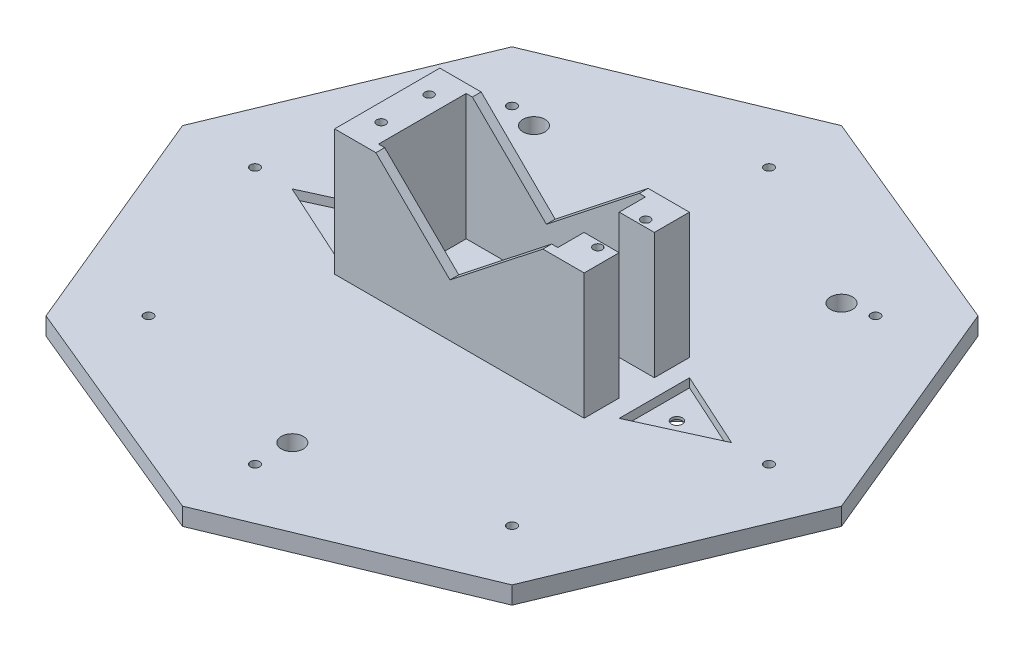
SolidWorks part; units mm, degrees
ref_plane "Ebene vorne" through (0, 0, 0) normal (0, 0, 1) x (1, 0, 0)
ref_plane "Ebene oben" through (0, 0, 0) normal (0, 1, 0) x (1, 0, 0)
ref_plane "Ebene rechts" through (0, 0, 0) normal (1, 0, 0) x (0, 0, -1)
sketch "Skizze2" plane through (0, 0, 0) normal (0, 1, 0) x (1, 0, 0)
  line L0 (-75, 0) -> (75, 0) construction
  line L1 (-55, 0) -> (55, 0) construction
  line L2 (0, -55) -> (0, 55) construction
  line L3 (-53.033, -53.033) -> (53.033, 53.033)
  line L4 (53.033, -53.033) -> (-53.033, 53.033)
  line L5 (-75, 0) -> (-53.033, 53.033)
  line L6 (-53.033, 53.033) -> (0, 75)
  line L7 (0, 75) -> (53.033, 53.033)
  line L8 (75, 0) -> (53.033, 53.033)
  line L9 (75, 0) -> (53.033, -53.033)
  line L10 (53.033, -53.033) -> (0, -75)
  line L11 (0, -75) -> (-53.033, -53.033)
  line L12 (-75, 0) -> (-53.033, -53.033)
  point P10 (0, 0)
  point P13 (0, 0)
  dimension "D1" = 150
  dimension "D2" = 75
  dimension "D3" = 150
  dimension "D4" = 150
  dimension "D5" = 45
  dimension "D6" = 45
  dimension "D7" = 75
  dimension "D8" = 75
extrude "Aufsatz-Linear austragen1" add sketch "Skizze2" along normal blind 3 and the other way blind 1 contours L7 L6 L4 L3 | L3 L0 L8 | L0 L4 L9 | L11 L10 L4 L3 | L5 L0 L4 | L0 L12 L3 region at (-42.6777, 0, -17.6777) region at (-42.6777, 0, 17.6777) region at (42.6777, 0, -17.6777) region at (0, 0, 42.6777) region at (0, 0, -42.6777) region at (42.6777, 0, 17.6777)
sketch "Skizze5" plane through (0, 0, 0) normal (0, 1, 0) x (1, 0, 0)
  line L0 (20.4, -4) -> (28.4, -4)
  line L1 (-20.4, -9.975) -> (20.4, -9.975)
  line L2 (-20.4, -9.975) -> (-20.4, 9.975)
  line L3 (-20.4, 9.975) -> (20.4, 9.975)
  line L4 (20.4, -9.975) -> (20.4, -4)
  line L5 (-20.4, -9.975) -> (20.4, 9.975) construction
  line L6 (-20.4, 9.975) -> (20.4, -9.975) construction
  line L7 (-28.4, -11.975) -> (28.4, -11.975)
  line L8 (-28.4, -11.975) -> (-28.4, 11.975)
  line L9 (-28.4, 11.975) -> (28.4, 11.975)
  line L10 (28.4, -11.975) -> (28.4, -4)
  line L11 (-28.4, -11.975) -> (28.4, 11.975) construction
  line L12 (-28.4, 11.975) -> (28.4, -11.975) construction
  line L13 (20.4, 4) -> (28.4, 4)
  line L14 (-2.2, 0) -> (2.2, 0) construction
  line L15 (20.4, 4) -> (20.4, 9.975)
  line L16 (28.4, 4) -> (28.4, 11.975)
  point P0 (0, 0)
  point P6 (0, 0)
  dimension "D1" = 40.8
  dimension "D2" = 19.95
  dimension "D3" = 2
  dimension "D4" = 8
  dimension "D5" = 4
  dimension "D6" = 4
extrude "Aufsatz-Linear austragen3" add sketch "Skizze5" along normal blind 31.65
sketch "Skizze6" plane through (0, 0, 11.975) normal (0, 0, 1) x (1, 0, 0)
  line L0 (-19, 31.65) -> (19, 31.65)
  line L1 (-28.4, 31.65) -> (28.4, 31.65) construction
  line L2 (19, 31.65) -> (-2.1527, 14.9945)
  line L3 (-2.1527, 14.9945) -> (-19, 31.65)
  line L4 (0, -2.2) -> (0, 2.2) construction
  point P5 (0, 31.65)
  dimension "D1" = 38
  dimension "D2" = 0
extrude "Schnitt-Linear austragen1" cut sketch "Skizze6" against normal blind 28.65
sketch "Skizze7" plane through (0, 3, 0) normal (0, 1, 0) x (1, 0, 0)
  line L0 (-17.9575, 0) -> (17.9575, 0) construction
  line L5 (-35, -40) -> (33.3537, 38.1186) construction
  line L6 (-33.3537, 38.1186) -> (35, -40) construction
  circle A0 centre (35, 40) radius 2.5
  circle A1 centre (-35, 40) radius 2.5
  circle A2 centre (0, -50) radius 2.5
  point P0 (0, 0)
  dimension "D3" = 5
  dimension "D4" = 5
  dimension "D5" = 5
  dimension "D6" = 50
  dimension "D1" = 80
  dimension "D2" = 70
extrude "Schnitt-Linear austragen2" cut sketch "Skizze7" against normal through all
sketch "Skizze8" plane through (0, 3, 0) normal (0, 1, 0) x (1, 0, 0)
  line L0 (-75, 0) -> (75, 0) construction
  line L7 (-32.4, 8.05) -> (-32.4, -8.05)
  line L8 (-44.1054, 2.719) -> (-32.4, -8.05) construction
  line L9 (-44.1054, -2.719) -> (-32.4, 8.05) construction
  line L12 (32.4, 8.0043) -> (32.4, -8.0043)
  line L15 (32.4, 8.0043) -> (44.0833, -2.6833) construction
  line L16 (32.4, -8.0043) -> (44.0833, 2.6833) construction
  line L17 (28.4, -11.975) -> (28.4, -4) construction
  line L18 (-28.4, 11.975) -> (-28.4, -11.975) construction
  line L19 (-50.0756, 0) -> (-32.4, -8.05)
  line L21 (-32.4, 8.05) -> (-50.0756, 0)
  line L22 (32.4, -8.0043) -> (49.9752, 0)
  line L23 (49.9752, 0) -> (32.4, 8.0043)
  line L24 (32.4, -8.0043) -> (32.4, 8.0043)
  point P2 (-41.15, 0)
  point P7 (41.15, 0)
  dimension "D1" = 4
  dimension "D2" = 4
  dimension "D3" = 16.1
extrude "Schnitt-Linear austragen6" cut sketch "Skizze8" against normal blind 2 contours L7 L21 L19 | L22 L23 L12 region at (-38.2919, 3, 0) region at (38.2584, 3, 0)
sketch "Skizze9" plane through (0, 31.65, 0) normal (0, 1, 0) x (1, 0, 0)
  circle A0 centre (-24.4, -5.375) radius 1
  circle A1 centre (-24.4, 5.525) radius 1
  circle A2 centre (24.9, 5.525) radius 1
  circle A3 centre (24.9, -5.375) radius 1
  dimension "D1" = 2
  dimension "D2" = 2
  dimension "D3" = 2
  dimension "D4" = 2
extrude "Schnitt-Linear austragen5" cut sketch "Skizze9" against normal blind 13.1
sketch "Skizze10" plane through (0, 1, 0) normal (0, 1, 0) x (1, 0, 0)
  line L1 (-0.013, 21.1078) -> (0.0217, -30.9037) construction
  line L7 (41.9977, 0.05) -> (22.7023, 0.05) construction
  line L8 (-28.4, 11.975) -> (-28.4, -11.975) construction
  line L9 (28.4, 4) -> (28.4, 11.975) construction
  circle A0 centre (-37.4878, 0) radius 1.25
  circle A1 centre (37.49, 0.05) radius 1.25
  dimension "D1" = 2.5
  dimension "D2" = 0
  dimension "D3" = 9.0878
  dimension "D4" = 9.09
extrude "Schnitt-Linear austragen7" cut sketch "Skizze10" against normal through all
sketch "Skizze11" plane through (0, -1, 0) normal (0, -1, 0) x (1, 0, 0)
  circle A0 centre (-37.4878, 0) radius 2.75
  circle A1 centre (37.49, -0.05) radius 2.75
  dimension "D1" = 5.5
  dimension "D2" = 5.5
extrude "Schnitt-Linear austragen8" cut sketch "Skizze11" against normal blind 1.4
sketch "Skizze14" plane through (0, 3, 0) normal (0, 1, 0) x (1, 0, 0)
  line L0 (0, 0) -> (-51.0988, 51.0988) construction
  line L1 (-51.0988, 51.0988) -> (0, 0) construction
  line L2 (0, 0) -> (44.6211, 44.6211) construction
  line L3 (44.6211, 44.6211) -> (0, 0) construction
  line L4 (0, 0) -> (42.9287, -42.9287) construction
  line L5 (42.9287, -42.9287) -> (0, 0) construction
  line L6 (0, 0) -> (-43.4336, -43.4336) construction
  circle A1 centre (-58.5, 0) radius 1.05
  circle A2 centre (0, 58.5) radius 1.05
  circle A3 centre (-41.3657, 41.3657) radius 1.05
  circle A4 centre (41.3657, 41.3657) radius 1.05
  circle A5 centre (58.5, 0) radius 1.05
  circle A6 centre (41.3657, -41.3657) radius 1.05
  circle A7 centre (-41.3657, -41.3657) radius 1.05
  circle A8 centre (0, -58.5) radius 1.05
  dimension "D2" = 2.1
  dimension "D3" = 2.1
  dimension "D4" = 2.1
  dimension "D5" = 2.1
  dimension "D6" = 2.1
  dimension "D7" = 2.1
  dimension "D8" = 2.1
extrude "Schnitt-Linear austragen9" cut sketch "Skizze14" against normal blind 10
